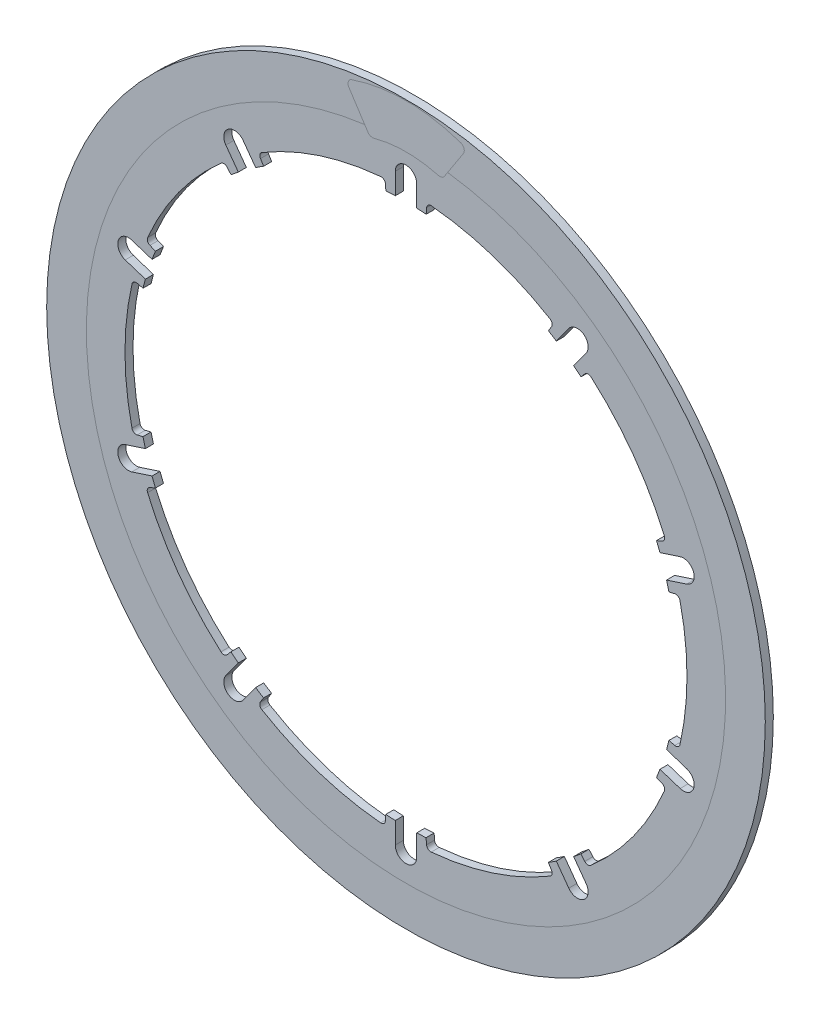
SolidWorks part; units mm, degrees
material "Gray Cast Iron"
ref_plane "Front Plane" through (0, 0, 0) normal (0, 0, 1) x (1, 0, 0)
ref_plane "Top Plane" through (0, 0, 0) normal (0, 1, 0) x (1, 0, 0)
ref_plane "Right Plane" through (0, 0, 0) normal (1, 0, 0) x (0, 0, -1)
sketch "Sketch1" plane through (0, 0, 0) normal (0, 0, 1) x (1, 0, 0)
  circle A0 centre (0, 0) radius 212.725
  dimension "D1" = 425.45
extrude "Boss-Extrude1" add sketch "Sketch1" along normal blind 4.7625
sketch3d "3DSketch3" [suppressed]
  line L4 (22.632, 184.3324, 30.7403) -> (33.9015, 201.686, 30.7403)
  line L5 (-33.9015, 201.686, 30.7403) -> (-22.632, 184.3324, 30.7403)
  arc A2 (-19.1346, 182.9983, 30.7403) -> (19.1346, 182.9983, 30.7403) centre (0, 112.7617, 30.7403) ccw
  spline S10 degree 3 poles (-22.632, 184.3324, 30.7403) (-22.5988, 184.2811, 30.7403) (-22.5293, 184.1805, 30.7403) (-22.4165, 184.0361, 30.7403) (-22.2957, 183.8983, 30.7403) (-22.1669, 183.7678, 30.7403) (-22.0309, 183.6449, 30.7403) (-21.8881, 183.53, 30.7403) (-21.7389, 183.4235, 30.7403) (-21.5838, 183.3258, 30.7403) (-21.4233, 183.2372, 30.7403) (-21.258, 183.1581, 30.7403) (-21.0428, 183.0698, 30.7403) (-20.7737, 182.9843, 30.7403) (-20.4488, 182.9172, 30.7403) (-20.1187, 182.8844, 30.7403) (-19.7871, 182.8865, 30.7403) (-19.4572, 182.9221, 30.7403) (-19.2411, 182.9691, 30.7403) (-19.1346, 182.9983, 30.7403) knots 0 0 0 0 0.045782 0.091558 0.137334 0.183113 0.228892 0.274672 0.32045 0.366227 0.412004 0.457782 0.503559 0.586301 0.669039 0.751777 0.834518 0.917255 1 1 1 1
  spline S11 degree 3 poles (19.1346, 182.9983, 30.7403) (19.1932, 182.9822, 30.7403) (19.3112, 182.9536, 30.7403) (19.4903, 182.9212, 30.7403) (19.6709, 182.8988, 30.7403) (19.8526, 182.8871, 30.7403) (20.0347, 182.8856, 30.7403) (20.2165, 182.8946, 30.7403) (20.3976, 182.9139, 30.7403) (20.5772, 182.9436, 30.7403) (20.7548, 182.9836, 30.7403) (20.9299, 183.0336, 30.7403) (21.1494, 183.1103, 30.7403) (21.4086, 183.2251, 30.7403) (21.6981, 183.3917, 30.7403) (21.9686, 183.5877, 30.7403) (22.2165, 183.8112, 30.7403) (22.4407, 184.059, 30.7403) (22.5716, 184.239, 30.7403) (22.632, 184.3324, 30.7403) knots 0 0 0 0 0.045473 0.090941 0.136409 0.181879 0.227351 0.272822 0.318291 0.36376 0.409229 0.454698 0.500168 0.583473 0.666777 0.750082 0.83339 0.916693 1 1 1 1
  spline S12 degree 3 poles (33.9015, 201.686, 30.7403) (33.9344, 201.7364, 30.7403) (33.9971, 201.839, 30.7403) (34.0817, 201.9976, 30.7403) (34.1575, 202.1609, 30.7403) (34.2237, 202.3283, 30.7403) (34.2804, 202.4992, 30.7403) (34.3274, 202.6731, 30.7403) (34.3646, 202.8492, 30.7403) (34.3917, 203.0273, 30.7403) (34.4086, 203.2065, 30.7403) (34.4153, 203.3864, 30.7403) (34.4119, 203.5665, 30.7403) (34.3756, 204.0435, 30.7403) (34.1614, 204.8075, 30.7403) (33.6821, 205.4852, 30.7403) (33.2752, 205.8566, 30.7403) (33.0454, 206.0314, 30.7403) (32.8006, 206.1843, 30.7403) (32.5436, 206.3149, 30.7403) (32.3643, 206.3858, 30.7403) (32.2732, 206.417, 30.7403) knots 0 0 0 0 0.031297 0.062588 0.093878 0.12517 0.156463 0.187756 0.219048 0.250339 0.28163 0.312921 0.344212 0.375504 0.562427 0.749344 0.799474 0.849606 0.899737 0.949865 1 1 1 1
  spline S13 degree 3 poles (32.2732, 206.417, 30.7403) (31.9592, 206.5252, 30.7403) (31.3303, 206.7384, 30.7403) (30.3838, 207.0486, 30.7403) (29.4343, 207.3495, 30.7403) (28.4817, 207.6406, 30.7403) (27.5262, 207.9222, 30.7403) (26.568, 208.1942, 30.7403) (25.6071, 208.4564, 30.7403) (24.6436, 208.7091, 30.7403) (23.6776, 208.952, 30.7403) (22.7092, 209.1852, 30.7403) (21.7385, 209.4087, 30.7403) (20.7656, 209.6224, 30.7403) (19.7906, 209.8263, 30.7403) (18.8136, 210.0204, 30.7403) (17.8348, 210.2046, 30.7403) (16.8541, 210.3791, 30.7403) (15.8717, 210.5436, 30.7403) (14.8877, 210.6982, 30.7403) (13.9022, 210.843, 30.7403) (12.9153, 210.9778, 30.7403) (11.927, 211.1027, 30.7403) (9.4532, 211.3901, 30.7403) (5.4798, 211.7206, 30.7403) (0, 211.8722, 30.7403) (-5.4798, 211.7206, 30.7403) (-9.7842, 211.3626, 30.7403) (-12.9159, 210.9828, 30.7403) (-14.8884, 210.7032, 30.7403) (-16.8549, 210.384, 30.7403) (-18.8146, 210.0253, 30.7403) (-20.7667, 209.6273, 30.7403) (-22.7103, 209.1901, 30.7403) (-24.6448, 208.7139, 30.7403) (-26.5694, 208.1991, 30.7403) (-28.483, 207.645, 30.7403) (-30.3853, 207.0535, 30.7403) (-31.6453, 206.6334, 30.7403) (-32.2732, 206.417, 30.7403) knots 0 0 0 0 0.015151 0.030302 0.045452 0.060603 0.075754 0.090905 0.106056 0.121206 0.136357 0.151508 0.166659 0.18181 0.19696 0.212111 0.227262 0.242413 0.257563 0.272714 0.287865 0.303016 0.318167 0.333317 0.41666 0.500002 0.583344 0.666687 0.696988 0.727289 0.75759 0.787892 0.818193 0.848494 0.878795 0.909096 0.939398 0.969699 1 1 1 1
  spline S14 degree 3 poles (-32.2732, 206.417, 30.7403) (-32.33, 206.3976, 30.7403) (-32.4424, 206.3554, 30.7403) (-32.6063, 206.2826, 30.7403) (-32.7663, 206.2007, 30.7403) (-32.9213, 206.1097, 30.7403) (-33.071, 206.0102, 30.7403) (-33.2148, 205.9024, 30.7403) (-33.3523, 205.7867, 30.7403) (-33.4831, 205.6634, 30.7403) (-33.6067, 205.5329, 30.7403) (-33.7226, 205.3956, 30.7403) (-33.8307, 205.2519, 30.7403) (-34.0967, 204.8533, 30.7403) (-34.3994, 204.1174, 30.7403) (-34.4385, 203.2861, 30.7403) (-34.346, 202.7423, 30.7403) (-34.2724, 202.4636, 30.7403) (-34.1736, 202.193, 30.7403) (-34.0515, 201.9325, 30.7403) (-33.9541, 201.7665, 30.7403) (-33.9015, 201.686, 30.7403) knots 0 0 0 0 0.031241 0.062476 0.093711 0.124947 0.156184 0.187421 0.218658 0.249893 0.281128 0.312363 0.343599 0.374835 0.562326 0.749809 0.799846 0.849885 0.899924 0.949958 1 1 1 1
  point P8 (0, 112.7617, -42.0561)
sketch "Sketch4" plane through (0, 0, 4.7625) normal (0, 0, 1) x (1, 0, 0)
  line L2 (22.7365, 184.6731) -> (34.006, 202.0267)
  line L3 (-33.7971, 202.0267) -> (-22.5275, 184.6731)
  arc A1 (19.2391, 183.339) -> (-19.0302, 183.339) centre (0.1045, 113.1023) ccw
  spline S5 degree 3 poles (34.006, 202.0267) (34.0389, 202.0771) (34.1016, 202.1797) (34.1862, 202.3383) (34.262, 202.5016) (34.3282, 202.669) (34.4038, 202.8969) (34.46, 203.1306) (34.4962, 203.3679) (34.5131, 203.5472) (34.5198, 203.7271) (34.5163, 203.9072) (34.4801, 204.3842) (34.2659, 205.1481) (33.7866, 205.8259) (33.3797, 206.1973) (33.1498, 206.3721) (32.9051, 206.525) (32.648, 206.6556) (32.4688, 206.7265) (32.3776, 206.7577) knots 0 0 0 0 0.031297 0.062588 0.093878 0.12517 0.156463 0.219048 0.250339 0.28163 0.312921 0.344212 0.375504 0.562427 0.749344 0.799474 0.849606 0.899737 0.949865 1 1 1 1
  spline S6 degree 3 poles (19.2391, 183.339) (19.2977, 183.3229) (19.4156, 183.2943) (19.5948, 183.2619) (19.7754, 183.2395) (19.9571, 183.2278) (20.1392, 183.2263) (20.321, 183.2353) (20.5021, 183.2546) (20.7416, 183.2942) (20.9771, 183.3543) (21.2539, 183.451) (21.5131, 183.5658) (21.8026, 183.7323) (22.073, 183.9284) (22.321, 184.1519) (22.5452, 184.3996) (22.6761, 184.5797) (22.7365, 184.6731) knots 0 0 0 0 0.045473 0.090941 0.136409 0.181879 0.227351 0.272822 0.318291 0.36376 0.454698 0.500168 0.583473 0.666777 0.750082 0.83339 0.916693 1 1 1 1
  spline S7 degree 3 poles (-22.5275, 184.6731) (-22.4943, 184.6218) (-22.4249, 184.5212) (-22.312, 184.3768) (-22.1912, 184.239) (-22.0624, 184.1085) (-21.9264, 183.9856) (-21.7836, 183.8707) (-21.6344, 183.7642) (-21.4276, 183.6339) (-21.2101, 183.5219) (-20.9383, 183.4105) (-20.6692, 183.325) (-20.3444, 183.2579) (-20.0142, 183.225) (-19.6827, 183.2272) (-19.3527, 183.2628) (-19.1367, 183.3098) (-19.0302, 183.339) knots 0 0 0 0 0.045782 0.091558 0.137334 0.183113 0.228892 0.274672 0.32045 0.366227 0.457782 0.503559 0.586301 0.669039 0.751777 0.834518 0.917255 1 1 1 1
  spline S8 degree 3 poles (-32.1687, 206.7577) (-32.2255, 206.7383) (-32.3379, 206.6961) (-32.5019, 206.6233) (-32.6618, 206.5414) (-32.8168, 206.4504) (-33.0164, 206.3177) (-33.2043, 206.1685) (-33.3786, 206.0041) (-33.5022, 205.8736) (-33.6182, 205.7363) (-33.7262, 205.5926) (-33.9922, 205.194) (-34.2949, 204.4581) (-34.3341, 203.6268) (-34.2415, 203.083) (-34.1679, 202.8043) (-34.0691, 202.5337) (-33.947, 202.2732) (-33.8496, 202.1072) (-33.7971, 202.0267) knots 0 0 0 0 0.031241 0.062476 0.093711 0.124947 0.156184 0.218658 0.249893 0.281128 0.312363 0.343599 0.374835 0.562326 0.749809 0.799846 0.849885 0.899924 0.949958 1 1 1 1
  spline S9 degree 3 poles (32.3776, 206.7577) (32.0637, 206.8659) (31.4348, 207.0791) (30.4883, 207.3893) (29.5388, 207.6902) (28.5862, 207.9813) (26.9938, 208.4506) (23.7904, 209.325) (20.2255, 210.1269) (16.6328, 210.7845) (14.6646, 211.0938) (13.0197, 211.3185) (12.0315, 211.4434) (9.5577, 211.7308) (5.5843, 212.0613) (0.1045, 212.2129) (-5.3753, 212.0613) (-9.6798, 211.7033) (-12.8114, 211.3235) (-14.7839, 211.0439) (-16.7504, 210.7247) (-18.7101, 210.366) (-20.6622, 209.968) (-22.6058, 209.5308) (-24.5403, 209.0546) (-26.4649, 208.5398) (-28.3785, 207.9857) (-30.2808, 207.3942) (-31.5409, 206.9741) (-32.1687, 206.7577) knots 0 0 0 0 0.015151 0.030302 0.045452 0.060603 0.075754 0.121206 0.212111 0.242413 0.287865 0.303016 0.318167 0.333317 0.41666 0.500002 0.583344 0.666687 0.696988 0.727289 0.75759 0.787892 0.818193 0.848494 0.878795 0.909096 0.939398 0.969699 1 1 1 1
sketch "Sketch8" plane through (0, 0, 0) normal (0, 0, -1) x (-1, 0, 0)
  circle A0 centre (0, 0) radius 166.37
  dimension "D1" = 332.74
extrude "Cut-Extrude1" cut sketch "Sketch8" against normal up to surface (4.7625 mm away) up to face at (212.725, 0, 4.7625)
sketch "Sketch9" plane through (0, 0, 0) normal (0, 0, -1) x (-1, 0, 0)
  line L1 (-6.35, 160.02) -> (6.35, 160.02)
  line L2 (-6.35, 160.02) -> (-6.35, 172.72)
  line L3 (-6.35, 172.72) -> (6.35, 172.72)
  line L4 (6.35, 160.02) -> (6.35, 172.72)
  line L5 (-6.35, 160.02) -> (6.35, 172.72) construction
  line L6 (-6.35, 172.72) -> (6.35, 160.02) construction
  circle A0 centre (0, 0) radius 166.37 construction
  circle A1 centre (0, 172.72) radius 6.35
  point P0 (0, 166.37)
  circle M4 centre (0, 0) radius 166.37
  dimension "D1" = 12.7
  dimension "D2" = 12.7
extrude "Cut-Extrude3" cut sketch "Sketch9" along direction (0, 0, 1) on the side against the normal up to surface (4.7625 mm away) contours L3 A1 | L3 A1 | A1 L4 M4 | A1 L2 M4 region at (4.9267, 167.7465, 0) region at (-4.9267, 167.7465, 0) region at (0, 175.415, 0) region at (0, 170.025, 0) up to face at (166.37, 0, 4.7625)
pattern_circular "CirPattern1" count 10 every 36 about axis through (0, 0, 0) along (0, 0, -1) of "Cut-Extrude3"
sketch "Sketch11" plane through (0, 0, 4.7625) normal (0, 0, 1) x (1, 0, 0)
  line L0 (-11.8938, 159.8321) -> (-12.1576, 163.3594)
  line L1 (-6.35, 166.2488) -> (-6.35, 160.1482)
  line L2 (6.35, 160.1482) -> (6.35, 166.2488)
  line L3 (11.9607, 159.8271) -> (12.2246, 163.3535)
  line L4 (6.35, 166.2488) -> (6.35, 172.72) construction
  arc A0 (11.9607, 159.8271) -> (6.35, 160.1482) centre (0, 0) ccw
  arc A1 (-6.35, 166.2488) -> (-92.5813, 138.2305) centre (0, 0) ccw construction
  arc A2 (92.5813, 138.2305) -> (6.35, 166.2488) centre (0, 0) ccw construction
  arc A3 (-6.35, 160.1482) -> (-11.8938, 159.8321) centre (0, 0) ccw
  arc A4 (-14.9183, 165.6998) -> (-92.5813, 138.2305) centre (0, 0) ccw
  arc A5 (92.5813, 138.2305) -> (14.9864, 165.6937) centre (0, 0) ccw
  arc A6 (-14.9183, 165.6998) -> (-12.1576, 163.3594) centre (-14.6905, 163.17) cw
  arc A7 (14.9864, 165.6937) -> (12.2246, 163.3535) centre (14.7576, 163.164) ccw
  arc M5 (-92.5813, 138.2305) -> (-6.35, 166.2488) centre (0, 0) cw
  arc M9 (6.35, 166.2488) -> (92.5813, 138.2305) centre (0, 0) cw
  dimension "D2" = 2.54
  dimension "D3" = 2.54
extrude "Boss-Extrude2" add sketch "Sketch11" against normal up to surface (4.7625 mm away) contours A0 L3 L2 M9 | A3 L1 L0 M5 region at (-9.3788, 163.1773, 4.7625) region at (9.4122, 163.1737, 4.7625) up to face at (0, 0, 0)
pattern_circular "CirPattern2" count 10 every 36 about axis through (0, 0, 4.7625) along (0, 0, -1) of "Boss-Extrude2"
sketch "Sketch15" [suppressed] plane through (0, 0, 6.35) normal (0, 0, 1) x (1, 0, 0)
  line L0 (-12.2165, 163.3739) -> (12.2261, 163.3732)
sketch "Sketch17" [suppressed] plane through (0, 0, 6.35) normal (0, 0, 1) x (1, 0, 0)
  line L0 (0, 0) -> (110.7699, 130.7089)
  line L1 (0, 0) -> (158.5451, 64.9479)
  arc A0 (161.9209, 73.4471) -> (119.8963, 131.2925) centre (0, 0) ccw
  arc A1 (161.9209, 73.4471) -> (158.5451, 64.9479) centre (156.138, 70.824) cw
  arc A2 (110.7699, 130.7089) -> (119.8963, 131.2925) centre (115.6143, 126.6035) cw
  dimension "D1" = 0
  dimension "D3" = 6.35
  dimension "D4" = 6.35
  dimension "D2" = 0
sketch "Sketch18" plane through (0, 0, 0) normal (0, 0, -1) x (-1, 0, 0)
  line L0 (33.7971, 202.0267) -> (22.5275, 184.6731) construction
  line L1 (-22.7365, 184.6731) -> (-34.006, 202.0267) construction
  line L2 (33.7971, 202.0267) -> (22.5275, 184.6731)
  line L3 (-22.7365, 184.6731) -> (-34.006, 202.0267)
  arc A0 (-24.6449, 187.6118) -> (24.4523, 187.637) centre (0, 0) ccw
  circle A1 centre (0, 0) radius 215.3351
  arc A2 (19.0302, 183.339) -> (-19.2391, 183.339) centre (-0.1045, 113.1023) ccw construction
  arc A3 (19.0302, 183.339) -> (-19.2391, 183.339) centre (-0.1045, 113.1023) ccw
  spline S0 degree 3 poles (-1450.1633, -1164.7301) (-59.0763, 285.4864) (32.2795, 197.129) (22.312, 184.3768) (22.1912, 184.239) (22.0624, 184.1085) (21.9264, 183.9856) (21.7836, 183.8707) (21.6344, 183.7642) (21.4276, 183.6339) (21.2101, 183.5219) (20.9383, 183.4105) (20.6692, 183.325) (20.3444, 183.2579) (20.0142, 183.225) (19.6827, 183.2272) (2.7527, 185.055) (8.5785, 322.4741) (2007.8128, 363.0309) knots -11.991769 -11.991769 -11.991769 -11.991769 0.045782 0.091558 0.137334 0.183113 0.228892 0.274672 0.32045 0.366227 0.457782 0.503559 0.586301 0.669039 0.751777 0.834518 0.917255 13.489507 13.489507 13.489507 13.489507 only from (22.5275, 184.6731) to (19.0302, 183.339) construction
  spline S1 degree 3 poles (-2016.3209, 153.4131) (-13.1774, 313.7756) (-3.6105, 186.1555) (-19.5948, 183.2619) (-19.7754, 183.2395) (-19.9571, 183.2278) (-20.1392, 183.2263) (-20.321, 183.2353) (-20.5021, 183.2546) (-20.7416, 183.2942) (-20.9771, 183.3543) (-21.2539, 183.451) (-21.5131, 183.5658) (-21.8026, 183.7323) (-22.073, 183.9284) (-22.321, 184.1519) (-33.7349, 196.7661) (61.8944, 295.2324) (1583.0626, -1002.353) knots -12.036429 -12.036429 -12.036429 -12.036429 0.045473 0.090941 0.136409 0.181879 0.227351 0.272822 0.318291 0.36376 0.454698 0.500168 0.583473 0.666777 0.750082 0.83339 0.916693 13.47468 13.47468 13.47468 13.47468 only from (-19.2391, 183.339) to (-22.7365, 184.6731) construction
  spline S2 degree 3 poles (-741.6985, 2071.3636) (51.5513, 215.3428) (-28.083, 190.8965) (-34.1862, 202.3383) (-34.262, 202.5016) (-34.3282, 202.669) (-34.4038, 202.8969) (-34.46, 203.1306) (-34.4962, 203.3679) (-34.5131, 203.5472) (-34.5198, 203.7271) (-34.5163, 203.9072) (-34.4801, 204.3842) (-34.2659, 205.1481) (-33.7866, 205.8259) (-33.3797, 206.1973) (-33.1498, 206.3721) (-32.9051, 206.525) (-19.4783, 213.3465) (41.9008, 122.514) (-1615.5521, -1012.0405) knots -6.679954 -6.679954 -6.679954 -6.679954 0.031297 0.062588 0.093878 0.12517 0.156463 0.219048 0.250339 0.28163 0.312921 0.344212 0.375504 0.562427 0.749344 0.799474 0.849606 0.899737 0.949865 8.706653 8.706653 8.706653 8.706653 only from (-34.006, 202.0267) to (-32.3776, 206.7577) construction
  spline S3 degree 3 poles (1661.243, 1259.3746) (-203.7859, -162.5293) (-163.0238, 163.9576) (-30.4883, 207.3893) (-29.5388, 207.6902) (-28.5862, 207.9813) (-26.9938, 208.4506) (-23.7904, 209.325) (-20.2255, 210.1269) (-16.6328, 210.7845) (-14.6646, 211.0938) (-13.0197, 211.3185) (-12.0315, 211.4434) (-9.5577, 211.7308) (-5.5843, 212.0613) (-0.1045, 212.2129) (5.3753, 212.0613) (9.6798, 211.7033) (12.8114, 211.3235) (14.7839, 211.0439) (16.7504, 210.7247) (18.7101, 210.366) (20.6622, 209.968) (22.6058, 209.5308) (24.5403, 209.0546) (26.4649, 208.5398) (28.3785, 207.9857) (189.3327, 157.9434) (218.1983, -304.2931) (-1891.4217, 643.6889) knots -6.319065 -6.319065 -6.319065 -6.319065 0.015151 0.030302 0.045452 0.060603 0.075754 0.121206 0.212111 0.242413 0.287865 0.303016 0.318167 0.333317 0.41666 0.500002 0.583344 0.666687 0.696988 0.727289 0.75759 0.787892 0.818193 0.848494 0.878795 0.909096 0.939398 0.969699 8.600273 8.600273 8.600273 8.600273 only from (-32.3776, 206.7577) to (32.1687, 206.7577) construction
  spline S4 degree 3 poles (1741.3262, -829.6052) (-26.9574, 143.7974) (20.6648, 211.8759) (32.5019, 206.6233) (32.6618, 206.5414) (32.8168, 206.4504) (33.0164, 206.3177) (33.2043, 206.1685) (33.3786, 206.0041) (33.5022, 205.8736) (33.6182, 205.7363) (33.7262, 205.5926) (33.9922, 205.194) (34.2949, 204.4581) (34.3341, 203.6268) (34.2415, 203.083) (34.1679, 202.8043) (34.0691, 202.5337) (27.687, 188.9067) (-76.4304, 222.6453) (533.1826, 2136.6237) knots -6.671073 -6.671073 -6.671073 -6.671073 0.031241 0.062476 0.093711 0.124947 0.156184 0.218658 0.249893 0.281128 0.312363 0.343599 0.374835 0.562326 0.749809 0.799846 0.849885 0.899924 0.949958 8.70048 8.70048 8.70048 8.70048 only from (32.1687, 206.7577) to (33.7971, 202.0267) construction
  spline S5 degree 3 poles (22.5275, 184.6731) (22.4943, 184.6218) (22.4249, 184.5212) (22.312, 184.3768) (22.1912, 184.239) (22.0624, 184.1085) (21.9264, 183.9856) (21.7836, 183.8707) (21.6344, 183.7642) (21.4276, 183.6339) (21.2101, 183.5219) (20.9383, 183.4105) (20.6692, 183.325) (20.3444, 183.2579) (20.0142, 183.225) (19.6827, 183.2272) (19.3527, 183.2628) (19.1367, 183.3098) (19.0302, 183.339) knots 0 0 0 0 0.045782 0.091558 0.137334 0.183113 0.228892 0.274672 0.32045 0.366227 0.457782 0.503559 0.586301 0.669039 0.751777 0.834518 0.917255 1 1 1 1
  spline S6 degree 3 poles (-19.2391, 183.339) (-19.2977, 183.3229) (-19.4156, 183.2943) (-19.5948, 183.2619) (-19.7754, 183.2395) (-19.9571, 183.2278) (-20.1392, 183.2263) (-20.321, 183.2353) (-20.5021, 183.2546) (-20.7416, 183.2942) (-20.9771, 183.3543) (-21.2539, 183.451) (-21.5131, 183.5658) (-21.8026, 183.7323) (-22.073, 183.9284) (-22.321, 184.1519) (-22.5452, 184.3996) (-22.6761, 184.5797) (-22.7365, 184.6731) knots 0 0 0 0 0.045473 0.090941 0.136409 0.181879 0.227351 0.272822 0.318291 0.36376 0.454698 0.500168 0.583473 0.666777 0.750082 0.83339 0.916693 1 1 1 1
  spline S7 degree 3 poles (-34.006, 202.0267) (-34.0389, 202.0771) (-34.1016, 202.1797) (-34.1862, 202.3383) (-34.262, 202.5016) (-34.3282, 202.669) (-34.4038, 202.8969) (-34.46, 203.1306) (-34.4962, 203.3679) (-34.5131, 203.5472) (-34.5198, 203.7271) (-34.5163, 203.9072) (-34.4801, 204.3842) (-34.2659, 205.1481) (-33.7866, 205.8259) (-33.3797, 206.1973) (-33.1498, 206.3721) (-32.9051, 206.525) (-32.648, 206.6556) (-32.4688, 206.7265) (-32.3776, 206.7577) knots 0 0 0 0 0.031297 0.062588 0.093878 0.12517 0.156463 0.219048 0.250339 0.28163 0.312921 0.344212 0.375504 0.562427 0.749344 0.799474 0.849606 0.899737 0.949865 1 1 1 1
  spline S8 degree 3 poles (-32.3776, 206.7577) (-32.0637, 206.8659) (-31.4348, 207.0791) (-30.4883, 207.3893) (-29.5388, 207.6902) (-28.5862, 207.9813) (-26.9938, 208.4506) (-23.7904, 209.325) (-20.2255, 210.1269) (-16.6328, 210.7845) (-14.6646, 211.0938) (-13.0197, 211.3185) (-12.0315, 211.4434) (-9.5577, 211.7308) (-5.5843, 212.0613) (-0.1045, 212.2129) (5.3753, 212.0613) (9.6798, 211.7033) (12.8114, 211.3235) (14.7839, 211.0439) (16.7504, 210.7247) (18.7101, 210.366) (20.6622, 209.968) (22.6058, 209.5308) (24.5403, 209.0546) (26.4649, 208.5398) (28.3785, 207.9857) (30.2808, 207.3942) (31.5409, 206.9741) (32.1687, 206.7577) knots 0 0 0 0 0.015151 0.030302 0.045452 0.060603 0.075754 0.121206 0.212111 0.242413 0.287865 0.303016 0.318167 0.333317 0.41666 0.500002 0.583344 0.666687 0.696988 0.727289 0.75759 0.787892 0.818193 0.848494 0.878795 0.909096 0.939398 0.969699 1 1 1 1
  spline S9 degree 3 poles (32.1687, 206.7577) (32.2255, 206.7383) (32.3379, 206.6961) (32.5019, 206.6233) (32.6618, 206.5414) (32.8168, 206.4504) (33.0164, 206.3177) (33.2043, 206.1685) (33.3786, 206.0041) (33.5022, 205.8736) (33.6182, 205.7363) (33.7262, 205.5926) (33.9922, 205.194) (34.2949, 204.4581) (34.3341, 203.6268) (34.2415, 203.083) (34.1679, 202.8043) (34.0691, 202.5337) (33.947, 202.2732) (33.8496, 202.1072) (33.7971, 202.0267) knots 0 0 0 0 0.031241 0.062476 0.093711 0.124947 0.156184 0.218658 0.249893 0.281128 0.312363 0.343599 0.374835 0.562326 0.749809 0.799846 0.849885 0.899924 0.949958 1 1 1 1
  dimension "D1" = 378.4471
  dimension "D2" = 430.6702
split line "Split Line3"
sketch "Sketch19" plane through (0, 0, 6.35) normal (0, 0, 1) x (1, 0, 0)
  line L0 (-33.7971, 202.0267) -> (-22.5275, 184.6731) construction
  line L1 (22.7365, 184.6731) -> (34.006, 202.0267) construction
  line L2 (-33.7971, 202.0267) -> (-22.5275, 184.6731)
  line L3 (22.7365, 184.6731) -> (34.006, 202.0267)
  arc A0 (-24.4523, 187.637) -> (24.6449, 187.6118) centre (0, 0) ccw
  circle A1 centre (0, 0) radius 215.3351
  arc A2 (19.2391, 183.339) -> (-19.0302, 183.339) centre (0.1045, 113.1023) ccw construction
  arc A3 (19.2391, 183.339) -> (-19.0302, 183.339) centre (0.1045, 113.1023) ccw
  spline S0 degree 3 poles (1450.1633, -1164.7301) (59.0763, 285.4864) (-32.2795, 197.129) (-22.312, 184.3768) (-22.1912, 184.239) (-22.0624, 184.1085) (-21.9264, 183.9856) (-21.7836, 183.8707) (-21.6344, 183.7642) (-21.4276, 183.6339) (-21.2101, 183.5219) (-20.9383, 183.4105) (-20.6692, 183.325) (-20.3444, 183.2579) (-20.0142, 183.225) (-19.6827, 183.2272) (-2.7527, 185.055) (-8.5785, 322.4741) (-2007.8128, 363.0309) knots -11.991769 -11.991769 -11.991769 -11.991769 0.045782 0.091558 0.137334 0.183113 0.228892 0.274672 0.32045 0.366227 0.457782 0.503559 0.586301 0.669039 0.751777 0.834518 0.917255 13.489507 13.489507 13.489507 13.489507 only from (-22.5275, 184.6731) to (-19.0302, 183.339) construction
  spline S1 degree 3 poles (-1741.3262, -829.6052) (26.9574, 143.7974) (-20.6648, 211.8759) (-32.5019, 206.6233) (-32.6618, 206.5414) (-32.8168, 206.4504) (-33.0164, 206.3177) (-33.2043, 206.1685) (-33.3786, 206.0041) (-33.5022, 205.8736) (-33.6182, 205.7363) (-33.7262, 205.5926) (-33.9922, 205.194) (-34.2949, 204.4581) (-34.3341, 203.6268) (-34.2415, 203.083) (-34.1679, 202.8043) (-34.0691, 202.5337) (-27.687, 188.9067) (76.4304, 222.6453) (-533.1826, 2136.6237) knots -6.671073 -6.671073 -6.671073 -6.671073 0.031241 0.062476 0.093711 0.124947 0.156184 0.218658 0.249893 0.281128 0.312363 0.343599 0.374835 0.562326 0.749809 0.799846 0.849885 0.899924 0.949958 8.70048 8.70048 8.70048 8.70048 only from (-32.1687, 206.7577) to (-33.7971, 202.0267) construction
  spline S2 degree 3 poles (-1661.243, 1259.3746) (203.7859, -162.5293) (163.0238, 163.9576) (30.4883, 207.3893) (29.5388, 207.6902) (28.5862, 207.9813) (26.9938, 208.4506) (23.7904, 209.325) (20.2255, 210.1269) (16.6328, 210.7845) (14.6646, 211.0938) (13.0197, 211.3185) (12.0315, 211.4434) (9.5577, 211.7308) (5.5843, 212.0613) (0.1045, 212.2129) (-5.3753, 212.0613) (-9.6798, 211.7033) (-12.8114, 211.3235) (-14.7839, 211.0439) (-16.7504, 210.7247) (-18.7101, 210.366) (-20.6622, 209.968) (-22.6058, 209.5308) (-24.5403, 209.0546) (-26.4649, 208.5398) (-28.3785, 207.9857) (-189.3327, 157.9434) (-218.1983, -304.2931) (1891.4217, 643.6889) knots -6.319065 -6.319065 -6.319065 -6.319065 0.015151 0.030302 0.045452 0.060603 0.075754 0.121206 0.212111 0.242413 0.287865 0.303016 0.318167 0.333317 0.41666 0.500002 0.583344 0.666687 0.696988 0.727289 0.75759 0.787892 0.818193 0.848494 0.878795 0.909096 0.939398 0.969699 8.600273 8.600273 8.600273 8.600273 only from (32.3776, 206.7577) to (-32.1687, 206.7577) construction
  spline S3 degree 3 poles (741.6985, 2071.3636) (-51.5513, 215.3428) (28.083, 190.8965) (34.1862, 202.3383) (34.262, 202.5016) (34.3282, 202.669) (34.4038, 202.8969) (34.46, 203.1306) (34.4962, 203.3679) (34.5131, 203.5472) (34.5198, 203.7271) (34.5163, 203.9072) (34.4801, 204.3842) (34.2659, 205.1481) (33.7866, 205.8259) (33.3797, 206.1973) (33.1498, 206.3721) (32.9051, 206.525) (19.4783, 213.3465) (-41.9008, 122.514) (1615.5521, -1012.0405) knots -6.679954 -6.679954 -6.679954 -6.679954 0.031297 0.062588 0.093878 0.12517 0.156463 0.219048 0.250339 0.28163 0.312921 0.344212 0.375504 0.562427 0.749344 0.799474 0.849606 0.899737 0.949865 8.706653 8.706653 8.706653 8.706653 only from (34.006, 202.0267) to (32.3776, 206.7577) construction
  spline S4 degree 3 poles (2016.3209, 153.4131) (13.1774, 313.7756) (3.6105, 186.1555) (19.5948, 183.2619) (19.7754, 183.2395) (19.9571, 183.2278) (20.1392, 183.2263) (20.321, 183.2353) (20.5021, 183.2546) (20.7416, 183.2942) (20.9771, 183.3543) (21.2539, 183.451) (21.5131, 183.5658) (21.8026, 183.7323) (22.073, 183.9284) (22.321, 184.1519) (33.7349, 196.7661) (-61.8944, 295.2324) (-1583.0626, -1002.353) knots -12.036429 -12.036429 -12.036429 -12.036429 0.045473 0.090941 0.136409 0.181879 0.227351 0.272822 0.318291 0.36376 0.454698 0.500168 0.583473 0.666777 0.750082 0.83339 0.916693 13.47468 13.47468 13.47468 13.47468 only from (19.2391, 183.339) to (22.7365, 184.6731) construction
  spline S5 degree 3 poles (-22.5275, 184.6731) (-22.4943, 184.6218) (-22.4249, 184.5212) (-22.312, 184.3768) (-22.1912, 184.239) (-22.0624, 184.1085) (-21.9264, 183.9856) (-21.7836, 183.8707) (-21.6344, 183.7642) (-21.4276, 183.6339) (-21.2101, 183.5219) (-20.9383, 183.4105) (-20.6692, 183.325) (-20.3444, 183.2579) (-20.0142, 183.225) (-19.6827, 183.2272) (-19.3527, 183.2628) (-19.1367, 183.3098) (-19.0302, 183.339) knots 0 0 0 0 0.045782 0.091558 0.137334 0.183113 0.228892 0.274672 0.32045 0.366227 0.457782 0.503559 0.586301 0.669039 0.751777 0.834518 0.917255 1 1 1 1
  spline S6 degree 3 poles (-32.1687, 206.7577) (-32.2255, 206.7383) (-32.3379, 206.6961) (-32.5019, 206.6233) (-32.6618, 206.5414) (-32.8168, 206.4504) (-33.0164, 206.3177) (-33.2043, 206.1685) (-33.3786, 206.0041) (-33.5022, 205.8736) (-33.6182, 205.7363) (-33.7262, 205.5926) (-33.9922, 205.194) (-34.2949, 204.4581) (-34.3341, 203.6268) (-34.2415, 203.083) (-34.1679, 202.8043) (-34.0691, 202.5337) (-33.947, 202.2732) (-33.8496, 202.1072) (-33.7971, 202.0267) knots 0 0 0 0 0.031241 0.062476 0.093711 0.124947 0.156184 0.218658 0.249893 0.281128 0.312363 0.343599 0.374835 0.562326 0.749809 0.799846 0.849885 0.899924 0.949958 1 1 1 1
  spline S7 degree 3 poles (32.3776, 206.7577) (32.0637, 206.8659) (31.4348, 207.0791) (30.4883, 207.3893) (29.5388, 207.6902) (28.5862, 207.9813) (26.9938, 208.4506) (23.7904, 209.325) (20.2255, 210.1269) (16.6328, 210.7845) (14.6646, 211.0938) (13.0197, 211.3185) (12.0315, 211.4434) (9.5577, 211.7308) (5.5843, 212.0613) (0.1045, 212.2129) (-5.3753, 212.0613) (-9.6798, 211.7033) (-12.8114, 211.3235) (-14.7839, 211.0439) (-16.7504, 210.7247) (-18.7101, 210.366) (-20.6622, 209.968) (-22.6058, 209.5308) (-24.5403, 209.0546) (-26.4649, 208.5398) (-28.3785, 207.9857) (-30.2808, 207.3942) (-31.5409, 206.9741) (-32.1687, 206.7577) knots 0 0 0 0 0.015151 0.030302 0.045452 0.060603 0.075754 0.121206 0.212111 0.242413 0.287865 0.303016 0.318167 0.333317 0.41666 0.500002 0.583344 0.666687 0.696988 0.727289 0.75759 0.787892 0.818193 0.848494 0.878795 0.909096 0.939398 0.969699 1 1 1 1
  spline S8 degree 3 poles (34.006, 202.0267) (34.0389, 202.0771) (34.1016, 202.1797) (34.1862, 202.3383) (34.262, 202.5016) (34.3282, 202.669) (34.4038, 202.8969) (34.46, 203.1306) (34.4962, 203.3679) (34.5131, 203.5472) (34.5198, 203.7271) (34.5163, 203.9072) (34.4801, 204.3842) (34.2659, 205.1481) (33.7866, 205.8259) (33.3797, 206.1973) (33.1498, 206.3721) (32.9051, 206.525) (32.648, 206.6556) (32.4688, 206.7265) (32.3776, 206.7577) knots 0 0 0 0 0.031297 0.062588 0.093878 0.12517 0.156463 0.219048 0.250339 0.28163 0.312921 0.344212 0.375504 0.562427 0.749344 0.799474 0.849606 0.899737 0.949865 1 1 1 1
  spline S9 degree 3 poles (19.2391, 183.339) (19.2977, 183.3229) (19.4156, 183.2943) (19.5948, 183.2619) (19.7754, 183.2395) (19.9571, 183.2278) (20.1392, 183.2263) (20.321, 183.2353) (20.5021, 183.2546) (20.7416, 183.2942) (20.9771, 183.3543) (21.2539, 183.451) (21.5131, 183.5658) (21.8026, 183.7323) (22.073, 183.9284) (22.321, 184.1519) (22.5452, 184.3996) (22.6761, 184.5797) (22.7365, 184.6731) knots 0 0 0 0 0.045473 0.090941 0.136409 0.181879 0.227351 0.272822 0.318291 0.36376 0.454698 0.500168 0.583473 0.666777 0.750082 0.83339 0.916693 1 1 1 1
  dimension "D1" = 378.4471
  dimension "D2" = 430.6702
split line "Split Line4"
sketch "Sketch20" plane through (0, 0, 0) normal (0, 0, -1) x (-1, 0, 0)
  line L1 (-3.8126, 161.2345) -> (3.8319, 161.2345)
  line L2 (-3.8126, 161.2345) -> (-3.8126, 169.2274)
  line L3 (-3.8126, 169.2274) -> (-0.9809, 169.2274)
  line L4 (3.8319, 161.2345) -> (3.8319, 169.2274)
  line L5 (1.2675, 169.2274) -> (3.8319, 169.2274)
  line L7 (-0.9809, 169.2274) -> (-0.9809, 180.1204)
  line L8 (-0.9809, 180.1204) -> (1.2675, 180.1204)
  line L9 (1.2675, 169.2274) -> (1.2675, 180.1204)
  circle A0 centre (0, 165.1) radius 3.175
  dimension "D1" = 6.35
  dimension "D2" = 165.1
extrude "Boss-Extrude3" [suppressed] add sketch "Sketch20" against normal blind 0.0254
pattern_circular "CirPattern3" [suppressed] count 10 over 360 of bodies 117
